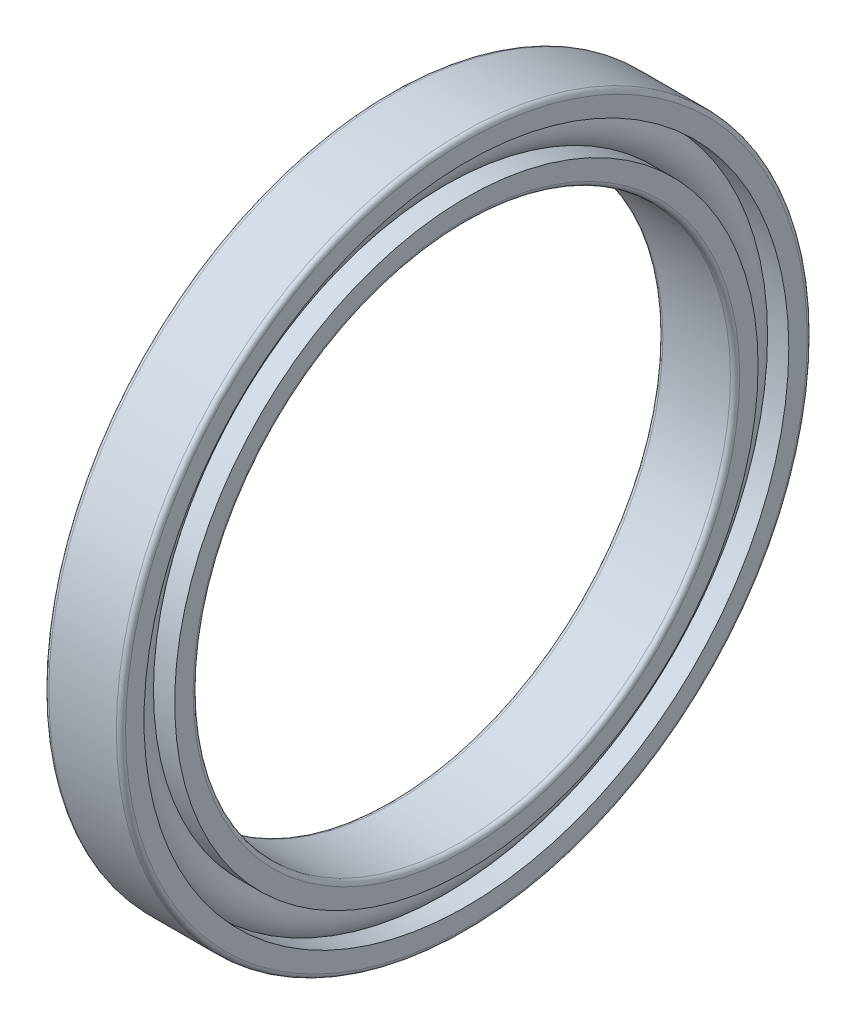
SolidWorks part; units mm, degrees
ref_plane "Plane1" through (0, 0, 0) normal (0, 0, 1) x (1, 0, 0)
ref_plane "Plane2" through (0, 0, 0) normal (0, 1, 0) x (1, 0, 0)
ref_plane "Plane3" through (0, 0, 0) normal (1, 0, 0) x (0, 0, -1)
other "Configuration Table"
sketch "Clipboard" plane through (0, 0, 0) normal (0, 0, 1) x (1, 0, 0)
  line L0 (-10, 0) -> (10, 0) construction
  line L1 (0, 0) -> (22.3471, -0.7804)
  line L2 (0, 0) -> (39.9756, 1.396)
  line L3 (0, 0) -> (22.3471, -0.7804)
  line L4 (0, 0) -> (-22.3573, -0.3902)
  dimension "BallCLRad" = 40
sketch "CagSpiSke" plane through (0, 0, 0) normal (0, 0, 1) x (1, 0, 0)
  line L0 (0.3, 39.5) -> (0.3, 40.5)
  line L1 (0.3, 40.5) -> (-0.3, 40.5)
  line L2 (-0.3, 40.5) -> (-0.3, 39.5)
  line L3 (-0.3, 39.5) -> (0.3, 39.5)
  line L4 (-20.6375, 0) -> (20.6375, 0) construction
  line L5 (0, 0) -> (0, 23.7692) construction
  dimension "OD" = 81
  dimension "ID" = 79
revolve "CageSpine" add sketch "CagSpiSke" angle 0.001 about L4 reverse direction yes
ref_axis "Axis1" through (-50, 0, 0) along (1, 0, 0)
sketch "CagBalSke" plane through (0, 0, 0) normal (0, 0, 1) x (1, 0, 0)
  line L0 (-3.3, 40) -> (3.3, 40)
  line L1 (-1.905, 40) -> (1.905, 40) construction
  line L2 (-10, 0) -> (10, 0) construction
  line L3 (0, 0) -> (0, 24) construction
  arc A0 (3.3, 40) -> (-3.3, 40) centre (0, 40) cw
  dimension "BallCLRad" = 40
revolve "CageBall" [suppressed] add sketch "CagBalSke" angle 360 about L1 reverse direction yes
pattern_circular "CageBalls" [suppressed] count 2 every 180 about axis through (-50, 0, 0) along (1, 0, 0)
sketch "CagTrmODSke" plane through (0, 0, 0) normal (0, 0, 1) x (1, 0, 0)
  line L0 (3.301, 40.5) -> (3.301, 43.301)
  line L1 (3.301, 43.301) -> (-3.301, 43.301)
  line L2 (-3.301, 43.301) -> (-3.301, 40.5)
  line L3 (-3.301, 40.5) -> (3.301, 40.5)
  line L4 (-20.6375, 0) -> (20.6375, 0) construction
  line L5 (0, 0) -> (0, 25) construction
  dimension "Width" = 6.602
  dimension "ID" = 81
  dimension "OD" = 86.602
revolve "CageTrimOD" [suppressed] cut sketch "CagTrmODSke" angle 360 about L4 reverse direction yes
sketch "CagTrmIDSke" plane through (0, 0, 0) normal (0, 0, 1) x (1, 0, 0)
  line L0 (3.301, 36.701) -> (3.301, 39.5)
  line L1 (3.301, 39.5) -> (-3.301, 39.5)
  line L2 (-3.301, 39.5) -> (-3.301, 36.701)
  line L3 (-3.301, 36.701) -> (3.301, 36.701)
  line L4 (-20.6375, 0) -> (20.6375, 0) construction
  line L5 (0, 0) -> (0, 25) construction
  dimension "Width" = 6.602
  dimension "ID" = 73.402
  dimension "OD" = 79
revolve "CageTrimID" [suppressed] cut sketch "CagTrmIDSke" angle 360 about L4 reverse direction yes
sketch "BalSimSke" plane through (0, 0, 0) normal (0, 0, 1) x (1, 0, 0)
  line L0 (-10, 0) -> (10, 0) construction
  line L1 (-10, 40) -> (10, 40) construction
  line L2 (0, 0) -> (0, 23) construction
  circle A0 centre (0, 40) radius 3
  dimension "BallCLRad" = 40
  dimension "Ball_diameter" = 6
revolve "BallsSimplified" add sketch "BalSimSke" angle 360 about L0
sketch "BalDetSke" plane through (0, 0, 0) normal (0, 0, 1) x (1, 0, 0)
  line L0 (-3, 40) -> (3, 40)
  line L1 (-1.905, 40) -> (1.905, 40) construction
  line L2 (0, 0) -> (0, 25) construction
  arc A0 (3, 40) -> (-3, 40) centre (0, 40) cw
  dimension "BallCLRad" = 40
  dimension "Ball_diameter" = 6
revolve "BallDetailed" [suppressed] add sketch "BalDetSke" angle 360 about L1 reverse direction yes
sketch "InnRacSke" plane through (0, 0, 0) normal (0, 0, 1) x (1, 0, 0)
  line L0 (-2.2024, 38) -> (-5, 38)
  line L1 (-5, 38) -> (-5, 35.6)
  line L2 (-4.4, 35) -> (4.4, 35)
  line L3 (5, 35.6) -> (5, 38)
  line L4 (5, 38) -> (2.2024, 38)
  line L5 (-20.6375, 0) -> (20.6375, 0) construction
  line L6 (0, 0) -> (0, 30) construction
  arc A0 (-5, 35.6) -> (-4.4, 35) centre (-4.4, 35.6) ccw
  arc A1 (4.4, 35) -> (5, 35.6) centre (4.4, 35.6) ccw
  arc A2 (2.2024, 38) -> (-2.2024, 38) centre (0, 40) cw
  dimension "BallCLRad" = 40
  dimension "Fillet_radius" = 0.6
  dimension "Ball_diameter" = 5.95
  dimension "ID" = 70
  dimension "OD" = 76
  dimension "Width" = 10
revolve "InnerRace" add sketch "InnRacSke" angle 360 about L5 reverse direction yes
sketch "OutRacSke" plane through (0, 0, 0) normal (0, 0, 1) x (1, 0, 0)
  line L0 (-2.2024, 42) -> (-5, 42)
  line L1 (-5, 42) -> (-5, 44.4)
  line L2 (-4.4, 45) -> (4.4, 45)
  line L3 (5, 44.4) -> (5, 42)
  line L4 (5, 42) -> (2.2024, 42)
  line L5 (-20.6375, 0) -> (20.6375, 0) construction
  line L6 (0, 0) -> (0, 30) construction
  arc A0 (-5, 44.4) -> (-4.4, 45) centre (-4.4, 44.4) cw
  arc A1 (4.4, 45) -> (5, 44.4) centre (4.4, 44.4) cw
  arc A2 (2.2024, 42) -> (-2.2024, 42) centre (0, 40) ccw
  dimension "BallCLRad" = 40
  dimension "Fillet_radius" = 0.6
  dimension "Ball_diameter" = 5.95
  dimension "Width" = 10
revolve "OuterRace" add sketch "OutRacSke" angle 360 about L5 reverse direction yes
pattern_circular "BallsDetailed" [suppressed] count 2 every 180 about axis through (-50, 0, 0) along (1, 0, 0)
equation "\"BallCLRad@Clipboard\" = ( \"OD@OutRacSke\" + \"ID@InnRacSke\" ) / 4"
equation "\"BallCLRad@BalSimSke\" = \"BallCLRad@Clipboard\""
equation "\"BallCLRad@BalDetSke\" = \"BallCLRad@Clipboard\""
equation "\"BallCLRad@InnRacSke\" = \"BallCLRad@Clipboard\""
equation "\"BallCLRad@OutRacSke\" = \"BallCLRad@Clipboard\""
equation "\"Ball_diameter@InnRacSke\" = \"Ball_diameter@BalDetSke\" - 0.05"
equation "\"Ball_diameter@OutRacSke\" = \"Ball_diameter@BalDetSke\" - 0.05"
equation "\"Ball_diameter@BalSimSke\" = \"Ball_diameter@BalDetSke\""
equation "\"Width@OutRacSke\" = \"Width@InnRacSke\""
equation "\"Fillet_radius@OutRacSke\" = \"Fillet_radius@InnRacSke\""
equation "\"Max_count@Clipboard\" = int( 3.14159265 / atn(( \"Ball_diameter@BalDetSke\" / 2) / sqr( \"BallCLRad@Clipboard\"  *  \"BallCLRad@Clipboard\" - ( \"Ball_diameter@BalDetSke\" / 2) *  ( \"Ball_diameter@BalDetSke\" / 2))))"
equation "\"Max_count@Clipboard\" = ((sgn( \"Max_count@Clipboard\" - \"Count@Clipboard\" )-1)*( \"Max_count@Clipboard\" - \"Count@Clipboard\" ))/-2+ \"Count@Clipboard\""
equation "\"Count@BallsDetailed\" = int( \"Show_count@Clipboard\" ) "
equation "\"Count@BallsDetailed\" = ((sgn( \"Count@BallsDetailed\" - \"Max_count@Clipboard\" )-1)*( \"Count@BallsDetailed\" - \"Max_count@Clipboard\" ))/-2+ \"Max_count@Clipboard\""
equation "\"Count@BallsDetailed\" = ((sgn( \"Count@BallsDetailed\" - \"Min_count@Clipboard\" )+1)*( \"Count@BallsDetailed\" - \"Min_count@Clipboard\"))/2 +\"Min_count@Clipboard\""
equation "\"Angle@BallsDetailed\" = 360.0 / \"Max_count@Clipboard\""
equation "\"BallCLRad@CagBalSke\" = \"BallCLRad@Clipboard\""
equation "\"Count@CageBalls\" = \"Count@BallsDetailed\""
equation "\"Angle@CageBalls\" = \"Angle@BallsDetailed\""
equation "\"Angle@CageSpine\" =  \"Angle@CageBalls\" * ( \"Count@CageBalls\" -1 + int( \"Count@CageBalls\" / \"Max_count@Clipboard\" ) )  + 0.001 -  int( \"Count@CageBalls\" / \"Max_count@Clipboard\" ) * 0.001"
equation "\"Angle@CageSpine\" =  \"Angle@CageSpine\" * int( \"Min_count@Clipboard\" / 2) + int(1 / \"Min_count@Clipboard\")  * 0.001"
equation "\"CageWallOD@CagBalSke\" =  \"Ball_diameter@BalDetSke\" * 1.1"
equation "\"Thickness@CagSpiSke\" =  \"Ball_diameter@BalDetSke\" * 0.1"
equation "\"OD@CagTrmODSke\" = \"BallCLRad@Clipboard\" * 2 + \"CageWallOD@CagBalSke\" + 0.002"
equation "\"ID@CagTrmODSke\" = \"BallCLRad@Clipboard\" * 2 + \"Ball_diameter@BalDetSke\" / 6"
equation "\"OD@CagTrmIDSke\" = \"BallCLRad@Clipboard\" * 2 - \"Ball_diameter@BalDetSke\" / 6"
equation "\"ID@CagTrmIDSke\" = \"BallCLRad@Clipboard\" * 2 - \"CageWallOD@CagBalSke\" + 0.002"
equation "\"OD@CagSpiSke\" = \"ID@CagTrmODSke\""
equation "\"ID@CagSpiSke\" = \"OD@CagTrmIDSke\""
equation "\"Width@CagTrmODSke\" = \"CageWallOD@CagBalSke\" + 0.002"
equation "\"Width@CagTrmIDSke\" = \"CageWallOD@CagBalSke\" + 0.002"
